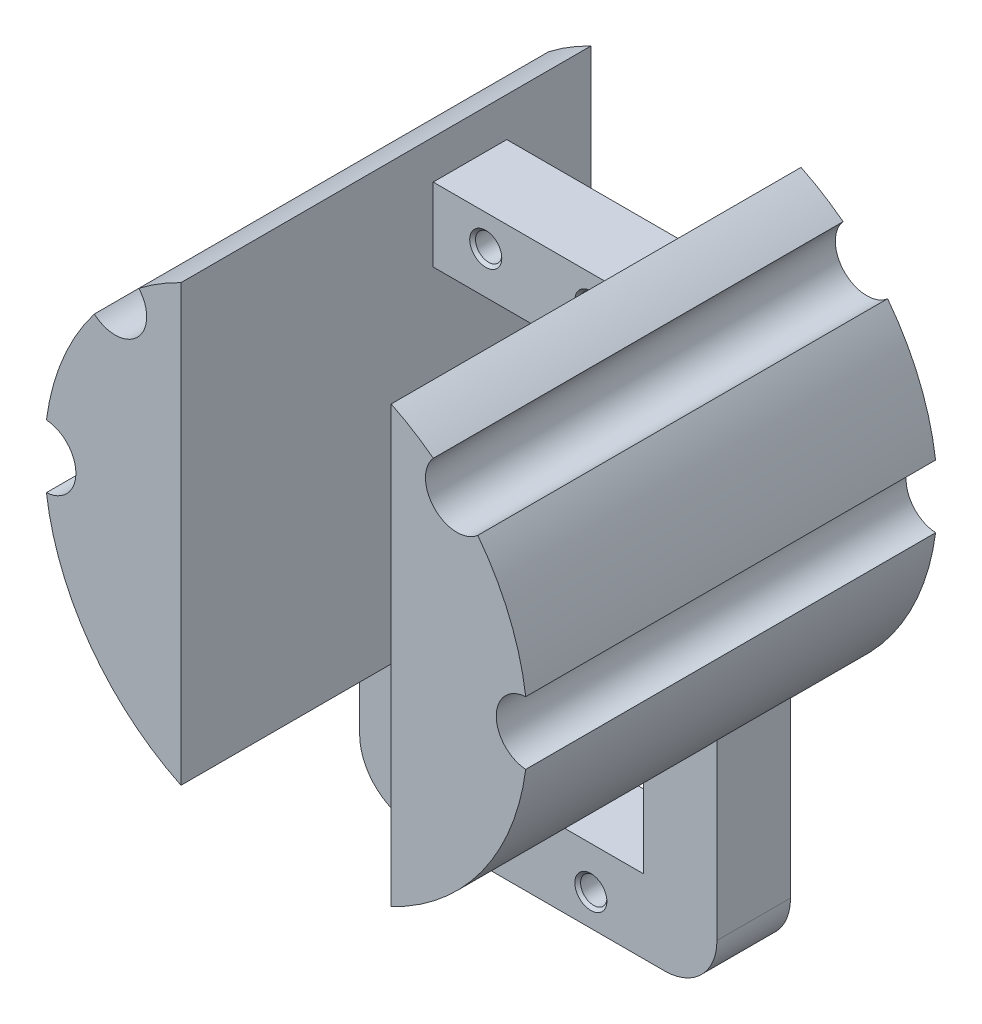
SolidWorks part; units mm, degrees
material "ПК/АБС"
ref_plane "Спереди" through (0, 0, 0) normal (0, 0, 1) x (1, 0, 0)
ref_plane "Сверху" through (0, 0, 0) normal (0, 1, 0) x (1, 0, 0)
ref_plane "Справа" through (0, 0, 0) normal (1, 0, 0) x (0, 0, -1)
sketch "Эскиз1" plane through (0, 0, 0) normal (0, 0, 1) x (1, 0, 0)
  line L0 (0, 0) -> (0, 23258.0729) construction
  line L1 (0, 0) -> (23258.0729, 0) construction
  line L2 (-10, 10) -> (10, 10)
  line L3 (10, 10) -> (10, -30)
  line L4 (10, -30) -> (-10, -30)
  line L5 (-10, -30) -> (-10, 10)
  line L6 (-17, 17) -> (17, 17)
  line L7 (17, 17) -> (17, -37)
  line L8 (17, -37) -> (-17, -37)
  line L9 (-17, -37) -> (-17, 17)
  point P7 (0, -30)
  dimension "D1" = 20
  dimension "D2" = 40
  dimension "D3" = 10
  dimension "D4" = 7
  dimension "D5" = 7
  dimension "D6" = 7
  dimension "D7" = 7
extrude "Бобышка-Вытянуть1" add sketch "Эскиз1" along normal blind 7
sketch "Эскиз2" plane through (0, 0, 0) normal (0, 0, 1) x (1, 0, 0)
  line L0 (10, -20.7123) -> (10, 20.7123)
  line L1 (10, -30) -> (10, 10) construction
  line L2 (-10, -20.7123) -> (-10, 20.7123)
  arc A0 (-10, 20.7123) -> (-10, -20.7123) centre (0, 0) ccw
  arc A1 (10, -20.7123) -> (10, 20.7123) centre (0, 0) ccw
  dimension "D1" = 46
extrude "Бобышка-Вытянуть2" add sketch "Эскиз2" along normal blind 31 and the other way blind 8
sketch "Эскиз3" plane through (0, 0, 31) normal (0, 0, 1) x (1, 0, 0)
  line L0 (-23, 0) -> (23, 0) construction
  line L1 (0, 0) -> (16.2635, 16.2635) construction
  line L2 (0, 0) -> (-16.2635, 16.2635) construction
  circle A0 centre (0, 0) radius 23 construction
  circle A1 centre (-23, 0) radius 3
  circle A2 centre (-16.2635, 16.2635) radius 3
  circle A3 centre (0, 23) radius 3 [skipped]
  circle A4 centre (16.2635, 16.2635) radius 3
  circle A5 centre (23, 0) radius 3
  circle A6 centre (16.2635, -16.2635) radius 3 [skipped]
  circle A7 centre (0, -23) radius 3 [skipped]
  circle A8 centre (-16.2635, -16.2635) radius 3 [skipped]
  point P25 (0, 0)
  dimension "D2" = 46
  dimension "D3" = 6
  dimension "D1" = 45
  dimension "D4" = 8
extrude "Вырез-Вытянуть1" cut sketch "Эскиз3" against normal through all
fillet "Скругление1" radius 5 2 edges at (-17, -37, 3.5) (17, -37, 3.5)
hole_wizard "Отверстие обработанное метчиком M3x0.51" positions "Эскиз4" profile "Эскиз5" tap size "M3x0.5" standard "HASCO Metric" end condition through all
sketch "Эскиз4" plane through (0, 0, 7) normal (0, 0, 1) x (1, 0, 0)
  line L0 (0, 0) -> (0, 50000) construction
  line L1 (0, -10) -> (-50000, -10) construction
  line L2 (10, 10) -> (-10, 10) construction
  line L4 (0, 14) -> (-50000, 14) construction
  line L5 (-5, -10) -> (-5, 49990) construction
  point P0 (-5, 14)
  point P19 (-5, 14.3)
  dimension "D1" = 20
  dimension "D2" = 24
  dimension "D3" = 5
sketch "Эскиз5" plane through (-5, 14, 7) normal (1, 0, 0) x (0, -1, 0)
  line L0 (0, 0) -> (0, 15)
  line L1 (0, 15) -> (1.25, 15)
  line L2 (1.25, 15) -> (1.25, 0.275)
  line L3 (1.25, 0.275) -> (1.525, 0)
  line L5 (1.525, 0) -> (0, 0)
  line L6 (-1.25, 0.275) -> (-1.525, 0) construction
  line L11 (0, -6.35) -> (0, 107.95) construction
  dimension "Диаметр проходного сверла" = 2.5
  dimension "Глубина проходного сверла" = 15
  dimension "Диаметр передней зенковки" = 3.05
  dimension "Угол передней зенковки" = 90
cosmetic thread "Отверстие резьбы1" parameters "D2"=3
pattern_linear "Линейный массив1" count 2 spacing 10 along (1, 0, 0) count 2 spacing 48 along (0, -1, 0) of "Отверстие обработанное метчиком M3x0.51"
